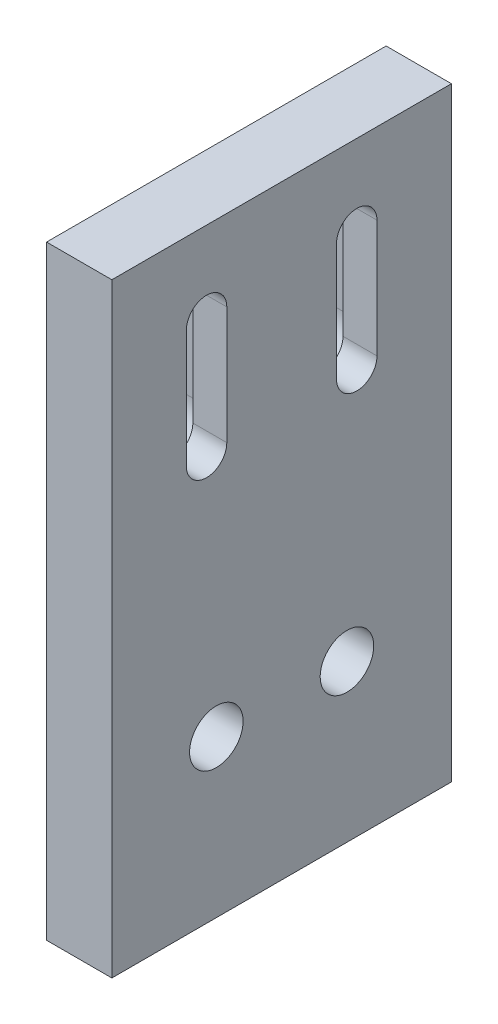
SolidWorks part; units mm, degrees
ref_plane "Front Plane" through (0, 0, 0) normal (0, 0, 1) x (1, 0, 0)
ref_plane "Top Plane" through (0, 0, 0) normal (0, 1, 0) x (1, 0, 0)
ref_plane "Right Plane" through (0, 0, 0) normal (1, 0, 0) x (0, 0, -1)
sketch "ProfileSketch1" plane through (0, 0, 0) normal (0, 0, 1) x (1, 0, 0)
  line L0 (0, 0) -> (5, 0)
  line L1 (5, 0) -> (5, 46.3)
  line L2 (5, 46.3) -> (0, 46.3)
  line L3 (0, 46.3) -> (0, 0)
  dimension "D1" = 46.3
  dimension "D4" = 5
extrude "Boss-Extrude1" add sketch "ProfileSketch1" along normal blind 26
sketch "ProbeSlidingMountSketch4" plane through (0, 0, 0) normal (-1, 0, 0) x (0, 0, 1)
  line L1 (26, 46.3) -> (0, 46.3) construction
  line L3 (5.7, 40.1) -> (5.7, 31.1)
  line L4 (8.8, 40.1) -> (8.8, 31.1)
  line L5 (17.2, 40.1) -> (17.2, 31.1)
  line L6 (20.3, 40.1) -> (20.3, 31.1)
  line L7 (0, 46.3) -> (0, 0) construction
  line L8 (26, 0) -> (0, 0) construction
  line L9 (26, 46.3) -> (26, 0) construction
  arc A0 (8.8, 40.1) -> (5.7, 40.1) centre (7.25, 40.1) ccw
  arc A1 (5.7, 31.1) -> (8.8, 31.1) centre (7.25, 31.1) ccw
  arc A2 (20.3, 40.1) -> (17.2, 40.1) centre (18.75, 40.1) ccw
  arc A3 (17.2, 31.1) -> (20.3, 31.1) centre (18.75, 31.1) ccw
  circle A4 centre (8, 12) radius 2.05
  circle A5 centre (18, 12) radius 2.05
  dimension "D1" = 3.1
  dimension "D6" = 4.1
  dimension "D2" = 9
  dimension "D7" = 19.1
  dimension "D4" = 11.5
  dimension "D5" = 7.25
  dimension "D9" = 7.25
  dimension "D10" = 12
  dimension "D11" = 10
  dimension "D12" = 8
  dimension "D13" = 8
  dimension "D3" = 6.2
extrude "ProbeSlidingMountCut-Extrude3" cut sketch "ProbeSlidingMountSketch4" against normal through all
sketch "ProbeSlidingMountChannelSketch5" plane through (0, 0, 0) normal (-1, 0, 0) x (0, 0, 1)
  line L0 (7.25, 40.1) -> (7.25, 31.1) construction
  line L1 (10.45, 40.1) -> (10.45, 31.1)
  line L2 (4.05, 40.1) -> (4.05, 31.1)
  line L3 (18.75, 40.1) -> (18.75, 31.1) construction
  line L4 (21.95, 40.1) -> (21.95, 31.1)
  line L5 (15.55, 40.1) -> (15.55, 31.1)
  arc A0 (10.45, 40.1) -> (4.05, 40.1) centre (7.25, 40.1) ccw
  arc A1 (4.05, 31.1) -> (10.45, 31.1) centre (7.25, 31.1) ccw
  arc A2 (21.95, 40.1) -> (15.55, 40.1) centre (18.75, 40.1) ccw
  arc A3 (15.55, 31.1) -> (21.95, 31.1) centre (18.75, 31.1) ccw
  point P4 (7.25, 35.6)
  point P9 (18.75, 35.6)
  dimension "D1" = 6.4
extrude "ProbeSlidingMountChanelCut-Extrude4" cut sketch "ProbeSlidingMountChannelSketch5" against normal blind 2.4
equation "\"ProbeMountHeight\"= + \"ProbeMountUpperHeight\" + \"ProbeMountingHoleSlotLength\" + \"ProbeMountMiddleHeight\" + \"ProbeMountLowerHeight\""
equation "\"D1@ProfileSketch1\"=\"ProbeMountHeight\" "
equation "\"D1@Boss-Extrude1\"= \"ProbeBodyWidth\""
equation "\"ProbeBodyWidth\"= \"InductiveProbeWidth\" + 8.3mm"
equation "\"ProbeMountUpperHeight\"= \"M3ScrewDiameter\" * 2"
equation "\"D4@ProfileSketch1\"=\"ProbeMountDepth\""
equation "\"M3ScrewButtonHeadHeight\"= 2.4mm"
equation "\"D1@ProbeSlidingMountSketch4\" = \"M3ScrewDiameter\""
equation "\"D2@ProbeSlidingMountSketch4\"=\"ProbeMountingHoleSlotLength\""
equation "\"M3ScrewDiameter\"= 3.1mm"
equation "\"ProbeMountDepth\"= \"M3HeatInsertHoleDepth\" + 1mm"
equation "\"M3ScrewButtonHeadDiameter\"= 5.9mm"
equation "\"D1@ProbeSlidingMountChannelSketch5\"=\"M3ScrewButtonHeadDiameter\"+ .5mm"
equation "\"D7@ProbeSlidingMountSketch4\"=\"ProbeMountMiddleHeight\""
equation "\"InductiveProbeWidth\"= 17.7mm"
equation "\"D5@ProbeSlidingMountSketch4\"=(\"ProbeBodyWidth\" - \"ProbeDistanceBetweenMountingHoles\")/2"
equation "\"ProbeDistanceBetweenMountingHoles\"= 11.5mm"
equation "\"D4@ProbeSlidingMountSketch4\"=\"ProbeDistanceBetweenMountingHoles\""
equation "\"M3HeatInsertHoleDepth\"= 4mm"
equation "\"InductiveProbeDistanceBetweenItsMountingHoles\"= 10mm"
equation "\"D12@ProbeSlidingMountSketch4\"=(\"ProbeBodyWidth\" - \"InductiveProbeDistanceBetweenItsMountingHoles\")/2"
equation "\"D11@ProbeSlidingMountSketch4\"=\"InductiveProbeDistanceBetweenItsMountingHoles\""
equation "\"M3HeatInsertHoleDiameter\"= 4mm + .1mm'Add .1mm for printing"
equation "\"ProbeMountingHoleSlotLength\"= 9mm"
equation "\"D3@ProbeSlidingMountSketch4\"=\"M3ScrewDiameter\" * 2"
equation "\"InductiveProbeTopHeight\"= 12mm"
equation "\"ProbeMountMiddleHeight\"= \"InductiveProbeTopHeight\" + \"M3ScrewDiameter\" * 2 + .9mm"
equation "\"ProbeMountLowerHeight\"= \"InductiveProbeTopHeight\""
equation "\"D6@ProbeSlidingMountSketch4\"=\"M3HeatInsertHoleDiameter\""
equation "\"D1@ProbeSlidingMountChanelCut-Extrude4\"=\"M3ScrewButtonHeadHeight\""
